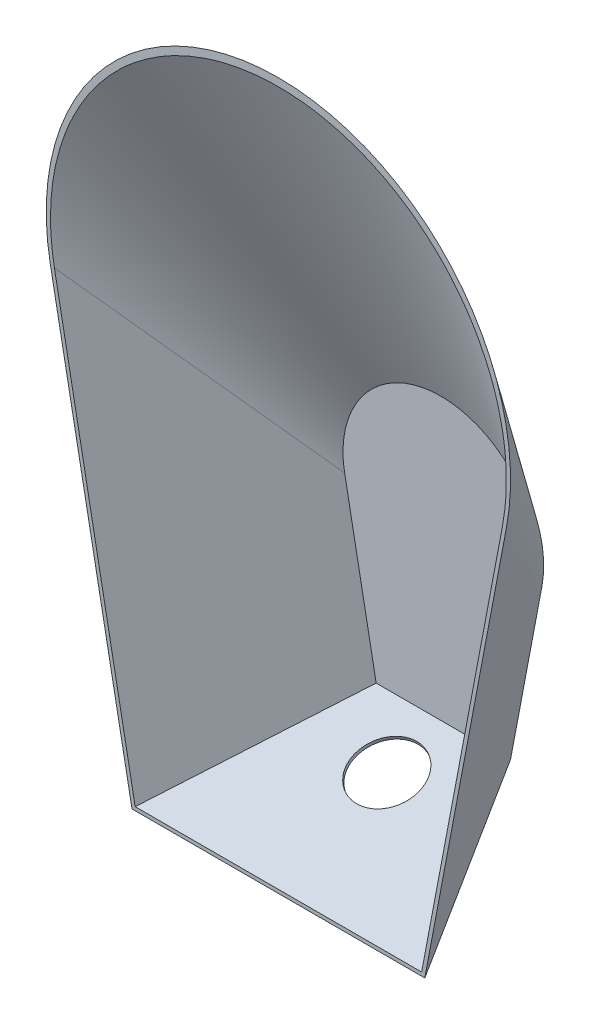
SolidWorks part; units mm, degrees
material "1.0038 (S235JRG2)"
ref_plane "Face" through (0, 0, 0) normal (0, 0, 1) x (1, 0, 0)
ref_plane "Dessus" through (0, 0, 0) normal (0, 1, 0) x (1, 0, 0)
ref_plane "Droite" through (0, 0, 0) normal (1, 0, 0) x (0, 0, -1)
ref_axis "X" through (-84.945, 0, 0) along (1, 0, 0)
ref_axis "Y" through (0, -55, 0) along (0, 1, 0)
ref_axis "Z" through (0, 0, 55) along (0, 0, -1)
sketch "Esquisse1" plane through (0, 0, 0) normal (0, 0, 1) x (1, 0, 0)
  line L0 (-29.4754, -5.5858) -> (-20, -55.5858)
  line L1 (-20, -55.5858) -> (20, -55.5858)
  line L2 (20, -55.5858) -> (29.4754, -5.5858)
  arc A0 (-29.4754, -5.5858) -> (29.4754, -5.5858) centre (0, 0) cw
  point P3 (0, -55.5858)
  dimension "D1" = 30
  dimension "D2" = 40
  dimension "D3" = 50
ref_plane "Plan1" through (0, 0, 50) normal (0, 0, 1) x (1, 0, 0)
sketch "Esquisse2" plane through (0, 0, 50) normal (0, 0, 1) x (1, 0, 0)
  line L0 (-44.1399, -75.5858) -> (44.1399, -75.5858)
  line L1 (44.1399, -75.5858) -> (68.7759, 54.4142)
  line L2 (20, -55.5858) -> (29.4754, -5.5858) construction
  line L3 (-44.1399, -75.5858) -> (-68.7759, 54.4142)
  line L4 (-29.4754, -5.5858) -> (-20, -55.5858) construction
  line L6 (-20, -55.5858) -> (20, -55.5858) construction
  arc A0 (-68.7759, 54.4142) -> (68.7759, 54.4142) centre (0, 67.4478) cw
  point P9 (0, -75.5858)
  dimension "D1" = 20
  dimension "D2" = 70
  dimension "D3" = 130
loft "Lissage1" add profiles "Esquisse2", "Esquisse1" connector at (-68.7759, 54.4142, 50) connector at (-29.4754, -5.5858, 0)
shell "Coque1" thickness 1 removed face at (0, -10.5858, 50)
sketch "Esquisse3" plane through (0, -47.9188, -19.1675) normal (0, -0.9285, -0.3714) x (1, 0, 0)
  line L0 (-44.1399, 74.4957) -> (20, 20.6441) construction
  line L1 (44.1399, 74.4957) -> (-20, 20.6441) construction
  circle A0 centre (-0.7629, 38.0765) radius 9.75
  dimension "D1" = 19.5
extrude "Enlèv. mat.-Extru.1" cut sketch "Esquisse3" against normal blind 10
